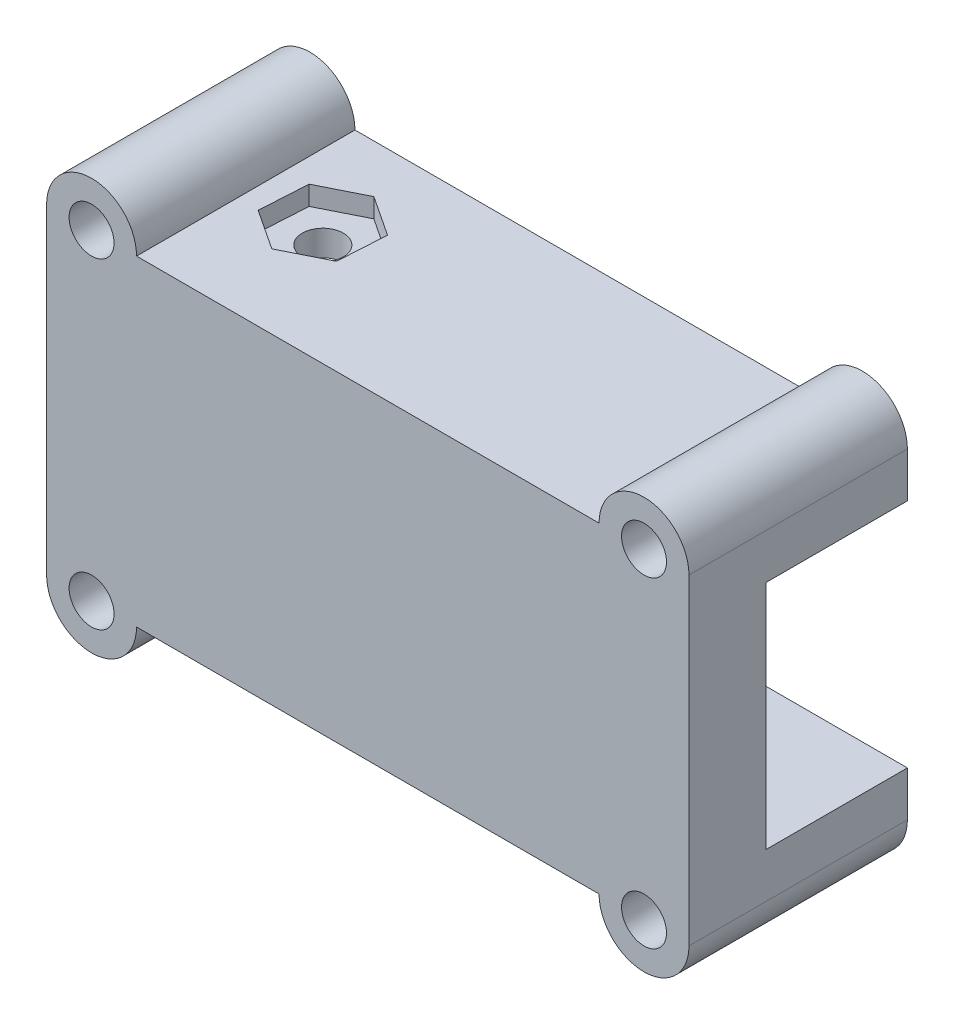
SolidWorks part; units mm, degrees
material "ABS"
ref_plane "Front Plane" through (0, 0, 0) normal (0, 0, 1) x (1, 0, 0)
ref_plane "Top Plane" through (0, 0, 0) normal (0, 1, 0) x (1, 0, 0)
ref_plane "Right Plane" through (0, 0, 0) normal (1, 0, 0) x (0, 0, -1)
sketch "Sketch1" plane through (0, 0, 0) normal (0, 0, 1) x (1, 0, 0)
  line L0 (-18, 12.5) -> (18, 12.5) construction
  line L1 (25, -12.5) -> (25, -8) construction
  line L2 (-18, -12.5) -> (18, -12.5) construction
  line L3 (-25, -12.5) -> (-25, 12.5) construction
  line L4 (-18, 12.5) -> (18, 12.5)
  line L5 (25, -12.5) -> (25, 12.5)
  line L6 (-18, -12.5) -> (18, -12.5)
  line L7 (-25, -12.5) -> (-25, 12.5)
  line L8 (-25, -9) -> (25, -9)
  line L9 (-18, -9) -> (18, -9) construction
  line L10 (-25, 9) -> (25, 9)
  line L11 (-18, 9) -> (18, 9) construction
  arc A0 (-18, 12.5) -> (-25, 12.5) centre (-21.5, 12.5) ccw construction
  arc A1 (25, 12.5) -> (18, 12.5) centre (21.5, 12.5) ccw construction
  arc A2 (18, -12.5) -> (25, -12.5) centre (21.5, -12.5) ccw construction
  arc A3 (-25, -12.5) -> (-18, -12.5) centre (-21.5, -12.5) ccw construction
  arc A4 (-18, 12.5) -> (-25, 12.5) centre (-21.5, 12.5) ccw
  arc A5 (25, 12.5) -> (18, 12.5) centre (21.5, 12.5) ccw
  arc A6 (18, -12.5) -> (25, -12.5) centre (21.5, -12.5) ccw
  arc A7 (-25, -12.5) -> (-18, -12.5) centre (-21.5, -12.5) ccw
  circle A8 centre (-21.5, -12.5) radius 1.75
  circle A9 centre (21.5, -12.5) radius 1.75
  circle A10 centre (21.5, 12.5) radius 1.75
  circle A11 centre (-21.5, 12.5) radius 1.75
  dimension "D1" = 3.5
  dimension "D2" = 3.5
  dimension "D3" = 3.5
extrude "Boss-Extrude1" add sketch "Sketch1" along normal blind 11 contours L5 A5 L4 A4 L7 L10 A11 A10 | L7 A7 L6 A6 L5 L8 A9 A8 region at (0, 11.2177, 0) region at (0, -11.2177, 0)
extrude "Boss-Extrude2" add sketch "Sketch1<3>" along normal blind 6 from surface contours L10 L7 L8 L5 | L5 A5 L4 A4 L7 L10 A11 A10 | L7 A7 L6 A6 L5 L8 A9 A8 region at (0, 11.2177, 0) region at (0, 0, 0) region at (0, -11.2177, 0) starting at face at (23.25, -12.5, 11)
sketch "Sketch1<3>" plane through (0, 0, 0) normal (0, 0, 1) x (1, 0, 0) same geometry as "Sketch1"
sketch "Sketch3" plane through (0, 0, 11) normal (0, 0, -1) x (-1, 0, 0)
  line L0 (-25, 0) -> (-15, 0) construction
  line L1 (-25, 9) -> (-25, -9) construction
  circle A0 centre (-15, 0) radius 4.25
  dimension "D1" = 8.5
  dimension "D2" = 10
extrude "Cut-Extrude1" cut sketch "Sketch3" against normal blind 5
sketch "Sketch4" plane through (0, -12.5, 0) normal (0, -1, 0) x (1, 0, 0)
  line L0 (-25, 17) -> (-25, 0) construction
  circle A0 centre (-13, 7.5) radius 1.6
  dimension "D1" = 3.2
  dimension "D2" = 3.5
  dimension "D3" = 12
extrude "Cut-Extrude2" cut sketch "Sketch4" against normal through all
sketch "Sketch5" plane through (0, 12.5, 0) normal (0, 1, 0) x (1, 0, 0)
  line L1 (-9.868, -9.5674) -> (-9.6436, -5.8213)
  line L2 (-9.6436, -5.8213) -> (-12.7756, -3.7539)
  line L3 (-12.7756, -3.7539) -> (-16.132, -5.4326)
  line L4 (-16.132, -5.4326) -> (-16.3564, -9.1787)
  line L5 (-16.3564, -9.1787) -> (-13.2244, -11.2461)
  line L6 (-13.2244, -11.2461) -> (-9.868, -9.5674)
  circle A0 centre (-13, -7.5) radius 3.25 construction
  dimension "D1" = 6.5
extrude "Cut-Extrude3" cut sketch "Sketch5" against normal blind 1.5
